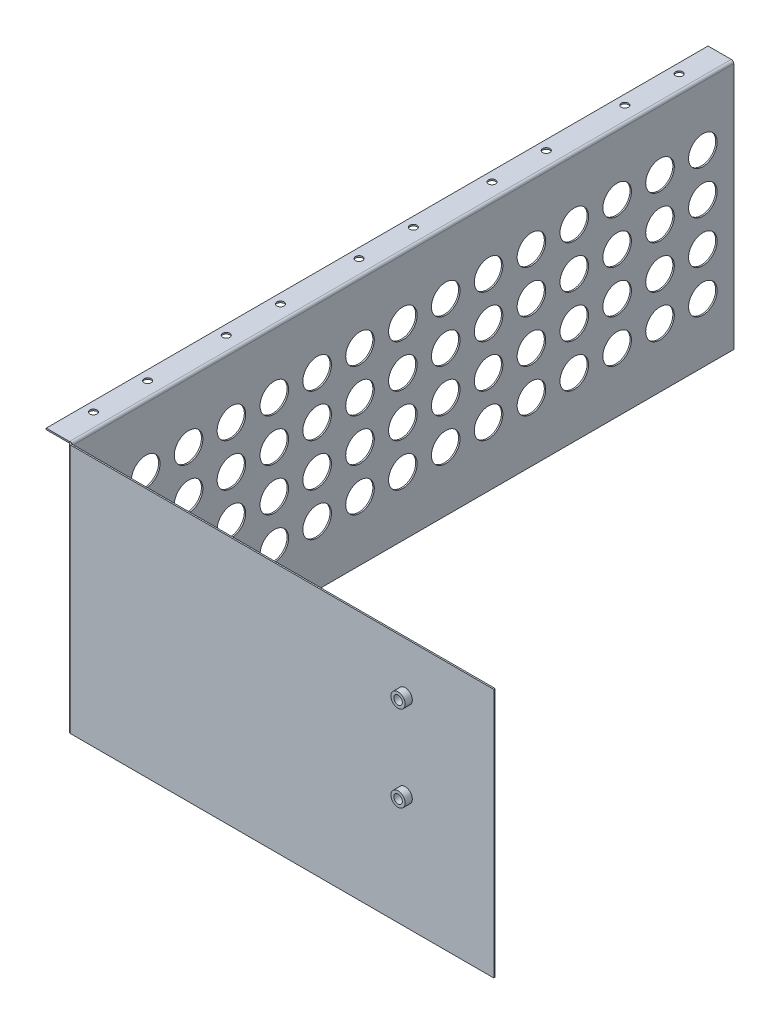
SolidWorks part; units mm, degrees
note: The reader was unsure of these and kept them because the rebuilt part matched: flange length of "Edge-Flange1", "Edge-Flange2".
ref_plane "Front Plane" through (0, 0, 0) normal (0, 0, 1) x (1, 0, 0)
ref_plane "Top Plane" through (0, 0, 0) normal (0, 1, 0) x (1, 0, 0)
ref_plane "Right Plane" through (0, 0, 0) normal (1, 0, 0) x (0, 0, -1)
sketch "Sketch1" plane through (0, 0, 0) normal (0, 0, 1) x (1, 0, 0)
  line L1 (-149, -87.5) -> (149, -87.5)
  line L2 (-149, -87.5) -> (-149, 87.5)
  line L3 (-149, 87.5) -> (149, 87.5)
  line L4 (149, -87.5) -> (149, 87.5)
  line L5 (-149, -87.5) -> (149, 87.5) construction
  line L6 (-149, 87.5) -> (149, -87.5) construction
  point P0 (0, 0)
  dimension "D1" = 298
  dimension "D2" = 175
base flange "Base-Flange1" sketch "Sketch1" thickness 1 reverse thickness direction no parameters "D1"=0.7366
sketch "Sketch6" [suppressed] plane through (0, 0, 0) normal (0, 0, 1) x (1, 0, 0)
  line L1 (-146, 110) -> (-646, 110)
  line L2 (-146, 110) -> (-146, -110)
  line L3 (-146, -110) -> (-646, -110)
  line L4 (-646, 110) -> (-646, -110)
  dimension "D1" = 500
sketch "Sketch9" [suppressed] plane through (0, 0, -1) normal (0, 0, -1) x (-1, 0, 0)
  line L0 (146, 110) -> (146, -110)
  line L1 (146, -110) -> (-146, -110) construction
  line L2 (146, -110) -> (146, 110) construction
edge flange "Edge-Flange1" sketch "Sketch12" flange angle 90 flange length 465 flange position material inside bend radius 0.7366 thickness 1 relief rectangular parameters "D6"=10
sketch "Sketch12" plane through (-149, 0, -1) normal (1, 0, 0) x (0, -1, 0)
  line L2 (-87.5, 0) -> (-87.5, 464)
  line L3 (-87.5, 464) -> (87.5, 464)
  line L4 (87.5, 464) -> (87.5, 0)
  line L5 (87.5, 0) -> (-87.5, 0) construction
  line L6 (87.5, 0) -> (-87.5, 0)
bend "EdgeBend1" bend radius 0.7366 bend angle 90 parameters "D5"=1
edge flange "Edge-Flange2" sketch "Sketch15" flange angle 90 flange length 18 flange position material inside bend radius 0.7366 thickness 1 relief none parameters "D6"=10
sketch "Sketch15" plane through (-149, 87.5, 0) normal (0, 1, 0) x (0, 0, -1)
  line L0 (465, 0) -> (1.7366, 0) construction
  line L1 (465, 0) -> (1.7366, 0)
  line L2 (1.7366, 0) -> (1.7366, 17)
  line L3 (1.7366, 17) -> (465, 17)
  line L4 (465, 17) -> (465, 0)
bend "EdgeBend2" bend radius 0.7366 bend angle 90 parameters "D5"=2
sketch "Sketch17" plane through (-149, 0, 0) normal (-1, 0, 0) x (0, 0, 1)
  circle A0 centre (-402.6069, 78.4539) radius 2.794
  circle A1 centre (-292.5995, 78.4539) radius 2.794
  circle A2 centre (-182.5921, 78.4539) radius 2.794
  circle A3 centre (-72.5847, 78.4539) radius 2.794
  circle A4 centre (-72.5847, 78.4539) radius 4.794
  circle A5 centre (-182.5921, 78.4539) radius 4.794
  circle A6 centre (-292.5995, 78.4539) radius 4.794
  circle A7 centre (-402.6069, 78.4539) radius 4.794
  dimension "D1" = 2
sketch "Sketch21" plane through (0, 0, 0) normal (0, 0, 1) x (1, 0, 0)
  line L0 (149, -87.5) -> (149, 87.5) construction
  line L1 (149, 87.5) -> (-147.2634, 87.5) construction
  circle A0 centre (87, 52.5) radius 3
  circle A2 centre (87, 52.5) radius 5
  circle A3 centre (87, -7.5) radius 3
  circle A4 centre (87, -7.5) radius 5
  dimension "D1" = 6
  dimension "D2" = 10
  dimension "D3" = 60
  dimension "D4" = 62
  dimension "D5" = 35
extrude "Boss-Extrude2" add sketch "Sketch21" along normal blind 5
sketch "Sketch22" plane through (-149, 0, 0) normal (-1, 0, 0) x (0, 0, 1)
  line L0 (-465, -87.5) -> (-465, 85.7634) construction
  circle A0 centre (-443.375, 44.1334) radius 10
  circle A1 centre (-413.375, 44.1334) radius 10
  circle A2 centre (-383.375, 44.1334) radius 10
  circle A3 centre (-353.375, 44.1334) radius 10
  circle A4 centre (-323.375, 44.1334) radius 10
  circle A5 centre (-293.375, 44.1334) radius 10
  circle A6 centre (-263.375, 44.1334) radius 10
  circle A7 centre (-233.375, 44.1334) radius 10
  circle A8 centre (-203.375, 44.1334) radius 10
  circle A9 centre (-173.375, 44.1334) radius 10
  circle A10 centre (-143.375, 44.1334) radius 10
  circle A11 centre (-113.375, 44.1334) radius 10
  circle A12 centre (-83.375, 44.1334) radius 10
  circle A22 centre (-413.375, 14.1334) radius 10
  circle A23 centre (-383.375, 14.1334) radius 10
  circle A24 centre (-353.375, 14.1334) radius 10
  circle A25 centre (-323.375, 14.1334) radius 10
  circle A26 centre (-293.375, 14.1334) radius 10
  circle A27 centre (-263.375, 14.1334) radius 10
  circle A28 centre (-233.375, 14.1334) radius 10
  circle A29 centre (-203.375, 14.1334) radius 10
  circle A30 centre (-173.375, 14.1334) radius 10
  circle A31 centre (-143.375, 14.1334) radius 10
  circle A32 centre (-113.375, 14.1334) radius 10
  circle A33 centre (-83.375, 14.1334) radius 10
  circle A43 centre (-413.375, -15.8666) radius 10
  circle A44 centre (-383.375, -15.8666) radius 10
  circle A45 centre (-353.375, -15.8666) radius 10
  circle A46 centre (-323.375, -15.8666) radius 10
  circle A47 centre (-293.375, -15.8666) radius 10
  circle A48 centre (-263.375, -15.8666) radius 10
  circle A49 centre (-233.375, -15.8666) radius 10
  circle A50 centre (-203.375, -15.8666) radius 10
  circle A51 centre (-173.375, -15.8666) radius 10
  circle A52 centre (-143.375, -15.8666) radius 10
  circle A53 centre (-113.375, -15.8666) radius 10
  circle A54 centre (-83.375, -15.8666) radius 10
  circle A64 centre (-413.375, -45.8666) radius 10
  circle A65 centre (-383.375, -45.8666) radius 10
  circle A66 centre (-353.375, -45.8666) radius 10
  circle A67 centre (-323.375, -45.8666) radius 10
  circle A68 centre (-293.375, -45.8666) radius 10
  circle A69 centre (-263.375, -45.8666) radius 10
  circle A70 centre (-233.375, -45.8666) radius 10
  circle A71 centre (-203.375, -45.8666) radius 10
  circle A72 centre (-173.375, -45.8666) radius 10
  circle A73 centre (-143.375, -45.8666) radius 10
  circle A74 centre (-113.375, -45.8666) radius 10
  circle A75 centre (-83.375, -45.8666) radius 10
  circle A148 centre (-443.375, 14.1334) radius 10
  circle A149 centre (-443.375, -15.8666) radius 10
  circle A150 centre (-443.375, -45.8666) radius 10
  circle A151 centre (-53.375, 44.1334) radius 10
  circle A152 centre (-23.375, 44.1334) radius 10
  circle A153 centre (-53.375, 14.1334) radius 10
  circle A154 centre (-23.375, 14.1334) radius 10
  circle A155 centre (-53.375, -15.8666) radius 10
  circle A156 centre (-23.375, -15.8666) radius 10
  circle A157 centre (-53.375, -45.8666) radius 10
  circle A158 centre (-23.375, -45.8666) radius 10
  dimension "D1" = 21.625
  dimension "D2" = 20
  dimension "D3" = 15
  dimension "D4" = 4
extrude "Cut-Extrude1" cut sketch "Sketch22" against normal blind 10 normal cut yes
sketch "Sketch24" plane through (0, 87.5, 0) normal (0, 1, 0) x (1, 0, 0)
  line L0 (-159.25, 438) -> (-159.25, 66)
  line L4 (-166, 465) -> (-166, 1.7366) construction
  line L6 (-149.7366, 465) -> (-166, 465) construction
  circle A0 centre (-159.25, 438) radius 2.5
  circle A1 centre (-159.25, 400) radius 2.5
  circle A2 centre (-159.25, 345) radius 2.5
  circle A3 centre (-159.25, 307) radius 2.5
  circle A4 centre (-159.25, 252) radius 2.5
  circle A5 centre (-159.25, 214) radius 2.5
  circle A6 centre (-159.25, 159) radius 2.5
  circle A7 centre (-159.25, 121) radius 2.5
  circle A8 centre (-159.25, 66) radius 2.5
  circle A9 centre (-159.25, 28) radius 2.5
  dimension "D3" = 6.75
  dimension "D5" = 27
  dimension "D7" = 120
  dimension "D9" = 213
  dimension "D11" = 306
  dimension "D12" = 399
  dimension "D2" = 2
  dimension "D4" = 2
  dimension "D6" = 2
  dimension "D8" = 2
  dimension "D10" = 2
extrude "Cut-Extrude2" cut sketch "Sketch24" along direction (0, -1, 0) on the side against the normal up to next (1 mm away) contours A0 | A1 | A2 | A3 | A4 | A5 | A6 | A7 | A8 | A9 normal cut yes
sketch "Bend-Lines1" [suppressed] plane through (0, 0, 0) normal (0, 1, 0) x (1, 0, 0)
sketch "Bounding-Box1" [suppressed] plane through (0, 0, 0) normal (0, 1, 0) x (1, 0, 0)
sheet metal parameters "Sheet-Metal1" thickness 1 parameters "D1"=0.7366
flat pattern "Flat-Pattern1" [suppressed]
sketch "Bend-Lines2" plane through (0, 0, 0) normal (0, 1, 0) x (1, 0, 0)
sketch3d "Bounding-Box2" [suppressed]
  line L0 (-146, -110, 0) -> (146, -110, 0) construction
  line L1 (-146, 110, 0) -> (146, 110, 0) construction
  line L2 (-146, -110, 0) -> (-146, 110, 0) construction
  line L3 (146, -110, 0) -> (146, 110, 0) construction
sheet metal parameters "Sheet-Metal3" thickness 1 parameters "D1"=0.7366
flat pattern "Flat-Pattern1"
sketch "Bend-Lines2" plane through (0, 0, 0) normal (0, 0, 1) x (1, 0, 0)
  line L0 (-145.2346, 87.5) -> (-145.2346, -87.5) construction
  line L1 (-145.2346, 87.5) -> (-145.2346, -87.5) construction
sketch3d "Bounding-Box2" [suppressed]
  line L0 (-603.4692, -87.5, 0) -> (146, -87.5, 0) construction
  line L1 (-603.4692, 87.5, 0) -> (146, 87.5, 0) construction
  line L2 (-603.4692, -87.5, 0) -> (-603.4692, 87.5, 0) construction
  line L3 (146, -87.5, 0) -> (146, 87.5, 0) construction
bend of the flat pattern "Flatten-<EdgeBend1>1"
sheet metal parameters "Sheet-Metal4" thickness 1 parameters "D1"=0.7366
flat pattern "Flat-Pattern1"
sketch "Bend-Lines2" plane through (0, 0, 0) normal (0, 0, 1) x (1, 0, 0)
  line L0 (-142.7346, 87.5) -> (-142.7346, -87.5) construction
  line L1 (-142.7346, 87.5) -> (-142.7346, -87.5) construction
  line L2 (-143.7058, 86.7346) -> (-606.9692, 86.7346) construction
  line L3 (-143.7058, 86.7346) -> (-606.9692, 86.7346) construction
sketch3d "Bounding-Box2" [suppressed]
  line L0 (-606.9692, -87.5, 0) -> (143.5, -87.5, 0) construction
  line L1 (-606.9692, 103.9692, 0) -> (143.5, 103.9692, 0) construction
  line L2 (-606.9692, -87.5, 0) -> (-606.9692, 103.9692, 0) construction
  line L3 (143.5, -87.5, 0) -> (143.5, 103.9692, 0) construction
bend of the flat pattern "Flatten-<EdgeBend1>1"
bend of the flat pattern "Flatten-<EdgeBend2>1"
sheet metal parameters "Sheet-Metal6" thickness 1 parameters "D1"=0.7366
flat pattern "Flat-Pattern1"
sketch "Bend-Lines2" plane through (0, 0, 0) normal (0, 0, 1) x (1, 0, 0)
  line L0 (-152.7346, 87.5) -> (-152.7346, -87.5) construction
  line L1 (-152.7346, 87.5) -> (-152.7346, -87.5) construction
  line L2 (-153.7058, 86.7346) -> (-616.9692, 86.7346) construction
  line L3 (-153.7058, 86.7346) -> (-616.9692, 86.7346) construction
sketch3d "Bounding-Box2" [suppressed]
  line L0 (-616.9692, -87.5, 0) -> (153.5, -87.5, 0) construction
  line L1 (-616.9692, 103.9692, 0) -> (153.5, 103.9692, 0) construction
  line L2 (-616.9692, -87.5, 0) -> (-616.9692, 103.9692, 0) construction
  line L3 (153.5, -87.5, 0) -> (153.5, 103.9692, 0) construction
bend of the flat pattern "Flatten-<EdgeBend1>1"
bend of the flat pattern "Flatten-<EdgeBend2>1"
sheet metal parameters "Sheet-Metal7" thickness 1 parameters "D1"=0.7366
flat pattern "Flat-Pattern1" [suppressed]
sketch "Bend-Lines2" plane through (0, 0, 0) normal (0, 0, 1) x (1, 0, 0)
  line L0 (-148.2346, 87.5) -> (-148.2346, -87.5) construction
  line L1 (-148.2346, 87.5) -> (-148.2346, -87.5) construction
  line L2 (-149.2058, 86.7346) -> (-612.4692, 86.7346) construction
  line L3 (-149.2058, 86.7346) -> (-612.4692, 86.7346) construction
sketch3d "Bounding-Box2" [suppressed]
  line L0 (-612.4692, -87.5, 0) -> (149, -87.5, 0) construction
  line L1 (-612.4692, 103.9692, 0) -> (149, 103.9692, 0) construction
  line L2 (-612.4692, -87.5, 0) -> (-612.4692, 103.9692, 0) construction
  line L3 (149, -87.5, 0) -> (149, 103.9692, 0) construction
bend of the flat pattern "Flatten-<EdgeBend1>1"
bend of the flat pattern "Flatten-<EdgeBend2>1"
sketch "Sketch17-1" [suppressed] plane through (-147.4692, 0, 0) normal (0, 0, 1) x (1, 0, 0)
  circle A0 centre (-402.6069, 78.4539) radius 2.794
  circle A1 centre (-292.5995, 78.4539) radius 2.794
  circle A2 centre (-182.5921, 78.4539) radius 2.794
  circle A3 centre (-72.5847, 78.4539) radius 2.794
  circle A4 centre (-72.5847, 78.4539) radius 4.794
  circle A5 centre (-182.5921, 78.4539) radius 4.794
  circle A6 centre (-292.5995, 78.4539) radius 4.794
  circle A7 centre (-402.6069, 78.4539) radius 4.794
sheet metal parameters "Sheet-Metal8" thickness 1 parameters "D1"=0.7366
flat pattern "Flat-Pattern1" [suppressed]
sketch "Bend-Lines2" plane through (0, 0, 0) normal (0, 0, 1) x (1, 0, 0)
  line L0 (-148.2346, 87.5) -> (-148.2346, -87.5) construction
  line L1 (-148.2346, 87.5) -> (-148.2346, -87.5) construction
  line L2 (-149.2058, 86.7346) -> (-612.4692, 86.7346) construction
  line L3 (-149.2058, 86.7346) -> (-612.4692, 86.7346) construction
sketch3d "Bounding-Box2" [suppressed]
  line L0 (-612.4692, -87.5, 0) -> (149, -87.5, 0) construction
  line L1 (-612.4692, 103.9692, 0) -> (149, 103.9692, 0) construction
  line L2 (-612.4692, -87.5, 0) -> (-612.4692, 103.9692, 0) construction
  line L3 (149, -87.5, 0) -> (149, 103.9692, 0) construction
bend of the flat pattern "Flatten-<EdgeBend1>1"
bend of the flat pattern "Flatten-<EdgeBend2>1"
sketch "Sketch17-1" [suppressed] plane through (-147.4692, 0, 0) normal (0, 0, 1) x (1, 0, 0)
  circle A0 centre (-402.6069, 78.4539) radius 2.794
  circle A1 centre (-292.5995, 78.4539) radius 2.794
  circle A2 centre (-182.5921, 78.4539) radius 2.794
  circle A3 centre (-72.5847, 78.4539) radius 2.794
  circle A4 centre (-72.5847, 78.4539) radius 4.794
  circle A5 centre (-182.5921, 78.4539) radius 4.794
  circle A6 centre (-292.5995, 78.4539) radius 4.794
  circle A7 centre (-402.6069, 78.4539) radius 4.794
